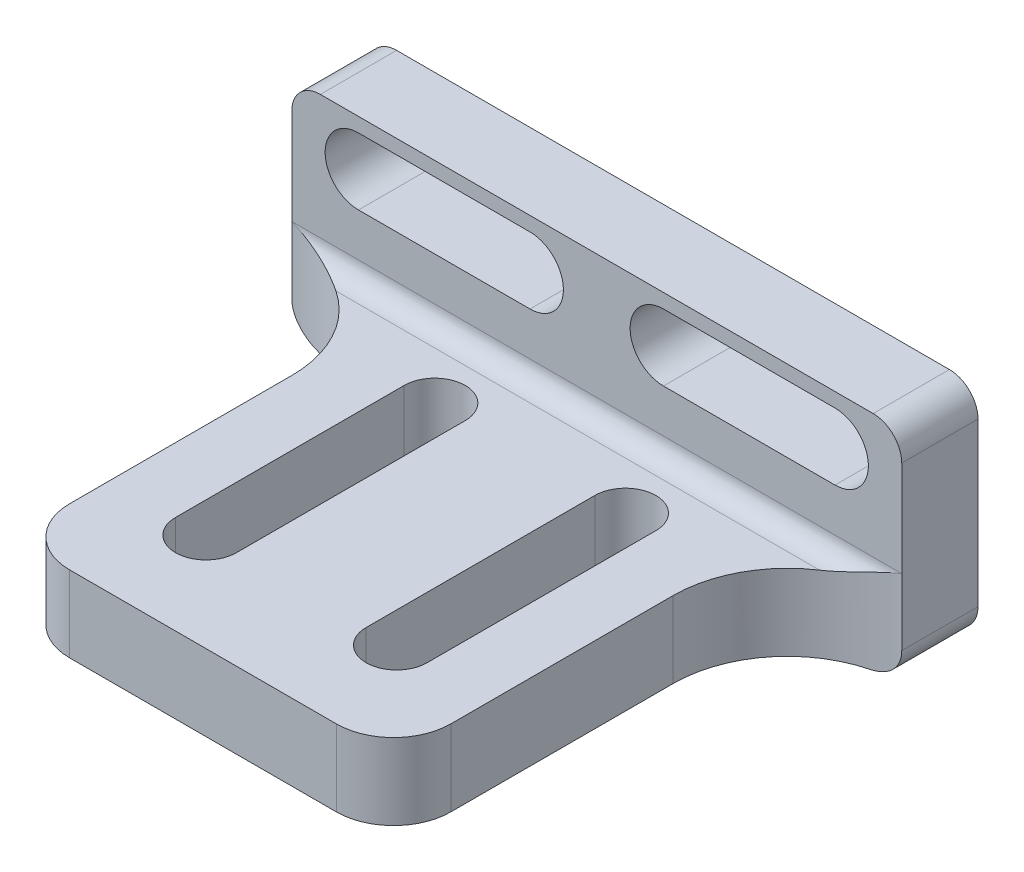
SolidWorks part; units mm, degrees
ref_plane "前视基准面" through (0, 0, 0) normal (0, 0, 1) x (1, 0, 0)
ref_plane "上视基准面" through (0, 0, 0) normal (0, 1, 0) x (1, 0, 0)
ref_plane "右视基准面" through (0, 0, 0) normal (1, 0, 0) x (0, 0, -1)
sketch "草图1" plane through (0, 0, 0) normal (0, 0, 1) x (1, 0, 0)
  line L0 (0, 148.5) -> (0, -94.9538) construction
  line L1 (105, -148.5) -> (-105, -148.5) construction
  line L2 (105, -148.5) -> (105, 148.5) construction
  line L3 (105, 148.5) -> (-105, 148.5) construction
  line L4 (-105, -148.5) -> (-105, 148.5) construction
  line L5 (105, -148.5) -> (-105, 148.5) construction
  line L6 (105, 148.5) -> (-105, -148.5) construction
  line L7 (35.8892, 121.6645) -> (-35.8892, 121.6645)
  line L8 (-35.8892, 121.6645) -> (-66.9017, 102.292)
  line L9 (-75, 40.9339) -> (-75, 31.2613)
  line L10 (-66.9017, 102.292) -> (-66.9017, 52.8701)
  line L11 (75, 40.9339) -> (75, 31.2613)
  line L12 (66.9017, 102.292) -> (66.9017, 52.8701)
  line L13 (35.8892, 121.6645) -> (66.9017, 102.292)
  line L14 (-75, 31.2613) -> (75, 31.2613)
  line L15 (-60, -148.5) -> (-60, -91.8129)
  line L16 (-75, 23.94) -> (75, 23.94)
  line L17 (-75, 23.94) -> (-75, 10.5626)
  line L18 (-38.8455, -105.5906) -> (-66.4608, -113.7617)
  line L19 (-66.4608, -113.7617) -> (-70.1743, -102.7328)
  line L20 (75, 23.94) -> (75, 10.5626)
  line L21 (66.4608, -113.7617) -> (70.1743, -102.7328)
  line L22 (38.8455, -105.5906) -> (66.4608, -113.7617)
  line L23 (-105, 93.0519) -> (105, 93.0519)
  line L24 (-105, 63.0519) -> (105, 63.0519)
  line L25 (-105, -90.0629) -> (-70.5337, -90.0629)
  line L26 (-105, -60.0629) -> (-67.4027, -60.0629)
  line L27 (60, -148.5) -> (60, 148.5)
  line L28 (-60, -58.3129) -> (-45, -58.3129)
  line L29 (-60, -61.8129) -> (-45, -61.8129)
  line L30 (-36, -58.3129) -> (-21, -58.3129)
  line L31 (-36, -61.8129) -> (-21, -61.8129)
  line L32 (-60, -88.3129) -> (-45, -88.3129)
  line L33 (-60, -91.8129) -> (-45, -91.8129)
  line L34 (-36, -88.3129) -> (-21, -88.3129)
  line L35 (-36, -91.8129) -> (-21, -91.8129)
  line L36 (-60, -58.3129) -> (-60, 148.5)
  line L37 (-19.25, -90.0629) -> (105, -90.0629)
  line L38 (-19.25, -60.0629) -> (19.25, -60.0629)
  line L39 (-60, -88.3129) -> (-60, -61.8129)
  line L40 (21, -58.3129) -> (36, -58.3129)
  line L41 (45, -58.3129) -> (60, -58.3129)
  line L42 (60, -61.8129) -> (45, -61.8129)
  line L43 (36, -61.8129) -> (21, -61.8129)
  line L44 (21, -88.3129) -> (36, -88.3129)
  line L45 (21, -91.8129) -> (36, -91.8129)
  line L46 (45, -88.3129) -> (60, -88.3129)
  line L47 (45, -91.8129) -> (60, -91.8129)
  line L48 (37.75, -60.0629) -> (43.25, -60.0629)
  line L49 (58.25, -60.0629) -> (105, -60.0629)
  line L50 (-60, 94.8019) -> (-45, 94.8019)
  line L51 (-36, 94.8019) -> (-21, 94.8019)
  line L52 (-60, 91.3019) -> (-45, 91.3019)
  line L53 (-36, 91.3019) -> (-21, 91.3019)
  line L54 (-60, 64.8019) -> (-45, 64.8019)
  line L55 (-60, 61.3019) -> (-45, 61.3019)
  line L56 (-36, 64.8019) -> (-21, 64.8019)
  line L57 (-36, 61.3019) -> (-21, 61.3019)
  line L58 (21, 94.8019) -> (36, 94.8019)
  line L59 (21, 91.3019) -> (36, 91.3019)
  line L60 (45, 94.8019) -> (60, 94.8019)
  line L61 (45, 91.3019) -> (60, 91.3019)
  line L62 (21, 61.3019) -> (36, 61.3019)
  line L63 (21, 64.8019) -> (36, 64.8019)
  line L64 (45, 61.3019) -> (60, 61.3019)
  line L65 (45, 64.8019) -> (60, 64.8019)
  line L66 (-33.1709, -104.7687) -> (33.1709, -104.7687)
  line L67 (0, -104.7687) -> (0, -148.5) construction
  arc A0 (-75, 40.9339) -> (-66.9017, 52.8701) centre (-79.7474, 52.8701) ccw
  arc A1 (75, 40.9339) -> (66.9017, 52.8701) centre (79.7474, 52.8701) cw
  arc A3 (-60, -88.3129) -> (-60, -91.8129) centre (-60, -90.0629) ccw
  arc A4 (-60, -58.3129) -> (-60, -61.8129) centre (-60, -60.0629) ccw
  circle A5 centre (-60, 63.0519) radius 1.75
  circle A6 centre (-60, 93.0519) radius 1.75
  circle A7 centre (60, 93.0519) radius 1.75
  circle A8 centre (60, 63.0519) radius 1.75
  arc A9 (60, -91.8129) -> (60, -88.3129) centre (60, -90.0629) ccw
  arc A10 (60, -61.8129) -> (60, -58.3129) centre (60, -60.0629) ccw
  arc A11 (-36, -58.3129) -> (-36, -61.8129) centre (-36, -60.0629) ccw
  arc A12 (-36, -88.3129) -> (-36, -91.8129) centre (-36, -90.0629) ccw
  arc A13 (36, -61.8129) -> (36, -58.3129) centre (36, -60.0629) ccw
  arc A14 (36, -91.8129) -> (36, -88.3129) centre (36, -90.0629) ccw
  arc A15 (-45, -61.8129) -> (-45, -58.3129) centre (-45, -60.0629) ccw
  arc A16 (-21, -61.8129) -> (-21, -58.3129) centre (-21, -60.0629) ccw
  arc A17 (-45, -91.8129) -> (-45, -88.3129) centre (-45, -90.0629) ccw
  arc A18 (-21, -91.8129) -> (-21, -88.3129) centre (-21, -90.0629) ccw
  arc A19 (45, -58.3129) -> (45, -61.8129) centre (45, -60.0629) ccw
  arc A20 (21, -58.3129) -> (21, -61.8129) centre (21, -60.0629) ccw
  arc A21 (21, -88.3129) -> (21, -91.8129) centre (21, -90.0629) ccw
  arc A22 (45, -88.3129) -> (45, -91.8129) centre (45, -90.0629) ccw
  circle A23 centre (-36, 93.0519) radius 1.75
  circle A24 centre (-36, 63.0519) radius 1.75
  circle A25 centre (36, 93.0519) radius 1.75
  circle A26 centre (36, 63.0519) radius 1.75
  circle A27 centre (-45, 93.0519) radius 1.75
  circle A28 centre (-21, 93.0519) radius 1.75
  circle A29 centre (-45, 63.0519) radius 1.75
  circle A30 centre (-21, 63.0519) radius 1.75
  circle A31 centre (21, 93.0519) radius 1.75
  circle A32 centre (21, 63.0519) radius 1.75
  circle A33 centre (45, 93.0519) radius 1.75
  circle A34 centre (45, 63.0519) radius 1.75
  arc A35 (33.1709, -104.7687) -> (38.8455, -105.5906) centre (33.1709, -124.7687) cw
  arc A36 (-33.1709, -104.7687) -> (-38.8455, -105.5906) centre (-33.1709, -124.7687) ccw
  spline S0 degree 3 poles (-75, 10.5626) (-72.6959, 1.9073) (-70.3396, -13.3728) (-67.1028, -43.6255) (-66.7657, -72.9327) (-71.8903, -95.1489) (-70.1743, -102.7328) knots 0 0 0 0 0.235247 0.406294 0.801186 1 1 1 1
  spline S1 degree 3 poles (75, 10.5626) (72.6959, 1.9073) (70.3396, -13.3728) (67.1028, -43.6255) (66.7657, -72.9327) (71.8903, -95.1489) (70.1743, -102.7328) knots 0 0 0 0 0.235247 0.406294 0.801186 1 1 1 1
  point P0 (0, 0)
  point P27 (0, 121.6645)
  point P42 (0, -94.0966)
  dimension "D1" = 60
  dimension "D4" = 20
  dimension "D5" = 24
  dimension "D7" = 24
  dimension "D9" = 15
  dimension "D10" = 15
  dimension "D13" = 24
  dimension "D17" = 15
  dimension "D2" = 30
  dimension "D3" = 30
  dimension "D6" = 24
  dimension "D8" = 24
  dimension "D11" = 15
  dimension "D12" = 15
  dimension "D14" = 24
  dimension "D15" = 24
  dimension "D16" = 24
  dimension "D18" = 15
  dimension "D19" = 15
  dimension "D20" = 15
  dimension "D21" = 15
  dimension "D22" = 15
  dimension "D23" = 15
  dimension "D24" = 15
  dimension "D25" = 15
  dimension "D26" = 15
  dimension "D27" = 15
  dimension "D28" = 15
  dimension "D29" = 3.5
  dimension "D30" = 3.5
  dimension "D31" = 3.5
extrude "凸台-拉伸1" add sketch "草图1" along normal blind 3 contours A34 L24 A26 L62 A32 A30 L57 A24 A29 L55 L36 L14 L27 L64 | A5 L24 L10 A0 L9 L14 L36 | A6 L23 L10 L24 A5 L36 | A6 L36 L8 L10 L23 | A33 L60 L27 L13 L7 L8 L36 L50 A27 L23 A23 L51 A28 A31 L58 A25 | A34 L65 L27 L61 A33 L23 A25 L59 A31 A28 L53 A23 A27 L52 L36 L54 A29 L24 A24 L56 A30 A32 L63 A26 | A7 L23 L12 L13 L27 | A8 L24 L12 L23 A7 L27 | A8 L27 L14 L11 A1 L12 L24 | A22 L46 L27 L42 A19 A13 L43 A20 A16 L31 A11 L30 L40 L41 L16 L36 L28 A15 L29 L39 L32 A17 L33 L15 L18 L22 L47 A14 L45 A21 A18 L35 A12 L34 | L17 S0 L19 L18 L15 A3 L39 A4 L36 L16 | S1 L20 L16 L27 A10 L49 | S1 L49 A10 L27 A9 L37 | S1 L37 A9 L27 L22 L21 region at (0, 106.7597, 0) region at (63.3118, 98.9762, 0) region at (-63.3118, 98.9762, 0) region at (63.5153, 78.0519, 0) region at (-63.5153, 78.0519, 0) region at (65.7633, 44.067, 0) region at (0, 78.0519, 0) region at (-65.7633, 44.067, 0) region at (0, 46.6707, 0) region at (0, -40.0712, 0) region at (65.6849, -11.6712, 0) region at (-65.3451, -38.0027, 0) region at (64.4303, -76.0355, 0) region at (65.0264, -100.7629, 0)
sketch "草图7" plane through (0, 0, 0) normal (0, 0, -1) x (-1, 0, 0)
  line L0 (0, 121.6645) -> (0, -104.7687) construction
  line L1 (-35.8892, 121.6645) -> (35.8892, 121.6645) construction
  line L2 (33.1709, -104.7687) -> (-33.1709, -104.7687) construction
  line L3 (0, 41.2613) -> (-21, 41.2613) construction
  line L4 (0, 41.2613) -> (21, 41.2613) construction
  line L5 (0, 13.94) -> (-21, 13.94) construction
  line L6 (0, 13.94) -> (21, 13.94) construction
  line L7 (75, 23.94) -> (-75, 23.94) construction
  line L8 (75, 31.2613) -> (-75, 31.2613) construction
  circle A0 centre (-21, 41.2613) radius 2.25
  circle A1 centre (21, 41.2613) radius 2.25
  circle A2 centre (-21, 13.94) radius 2.25
  circle A3 centre (21, 13.94) radius 2.25
  dimension "D1" = 10
  dimension "D2" = 10
extrude "切除-拉伸2" cut sketch "草图7" against normal through all
sketch "草图8" plane through (0, 0, 3) normal (0, 0, 1) x (1, 0, 0)
  line L0 (0, 121.6645) -> (0, -1.9696) construction
  line L1 (35.8892, 121.6645) -> (-35.8892, 121.6645) construction
  line L2 (-33.1709, -104.7687) -> (33.1709, -104.7687) construction
  line L3 (-33.409, 20.409) -> (-12.6214, -0.3786)
  line L4 (31.818, -51.182) -> (-31.818, -51.182)
  line L5 (35, -48) -> (35, 15.6418)
  line L8 (-35, 18.818) -> (-12.6214, -3.5605) construction
  line L9 (-33.409, -52.773) -> (-12.5737, -31.9377)
  line L10 (-36.591, 17.227) -> (-15.8034, -3.5605)
  line L11 (33.4105, 20.4105) -> (12.573, -0.427)
  line L12 (15.803, -3.5609) -> (36.5881, 17.2241)
  line L13 (31.8195, 18.8195) -> (-31.818, 18.818)
  line L14 (-15.8038, -28.8038) -> (-36.591, -49.591)
  line L15 (12.5534, -31.9174) -> (33.409, -52.773)
  line L16 (34.9993, 18.8173) -> (12.6207, -3.5613) construction
  line L17 (0, -30.3951) -> (0, -104.7687) construction
  line L18 (-35, -48) -> (-35, 15.636)
  line L19 (-11.9624, -1.9696) -> (-14.2124, -1.9696) construction
  line L20 (15.8034, -28.8034) -> (36.591, -49.591)
  line L21 (14.2117, -30.3951) -> (11.9607, -30.3951) construction
  line L22 (14.2117, -30.3951) -> (14.2117, -28.1441) construction
  line L23 (14.2117, -1.9696) -> (11.9612, -1.9696) construction
  line L24 (-14.2124, -30.3951) -> (-14.2124, -28.1446) construction
  line L25 (14.2117, -30.3951) -> (12.62, -28.8034) construction
  line L26 (14.2117, -1.9696) -> (12.6204, -3.5609) construction
  line L27 (12.6207, -28.8027) -> (35, -51.182) construction
  line L28 (-12.6215, -3.5606) -> (-14.2124, -1.9696) construction
  line L29 (-14.2124, -4.2196) -> (-14.2124, -1.9696) construction
  line L30 (-12.6214, -28.8034) -> (-35, -51.182) construction
  line L31 (-12.6211, -28.8037) -> (-14.2124, -30.3951) construction
  line L32 (-11.9619, -30.3951) -> (-14.2124, -30.3951) construction
  line L33 (14.2117, -4.2201) -> (14.2117, -1.9696) construction
  line L34 (11.0312, -30.3951) -> (0, -30.3951) construction
  arc A0 (-33.409, 20.409) -> (-36.591, 17.227) centre (-35, 18.818) ccw
  arc A1 (36.5881, 17.2241) -> (33.4105, 20.4105) centre (34.9993, 18.8173) ccw
  arc A2 (-36.591, -49.591) -> (-33.409, -52.773) centre (-35, -51.182) ccw
  arc A3 (33.409, -52.773) -> (36.591, -49.591) centre (35, -51.182) ccw
  arc A4 (-15.8034, -3.5605) -> (-12.6214, -0.3786) centre (-14.2124, -1.9696) ccw
  arc A5 (12.6692, -0.3308) -> (15.803, -3.5609) centre (14.2117, -1.9696) ccw
  arc A6 (-12.6699, -32.0338) -> (-15.8038, -28.8038) centre (-14.2124, -30.3951) ccw
  arc A7 (15.8034, -28.8034) -> (12.6894, -32.0534) centre (14.2117, -30.3951) ccw
  circle A8 centre (-0.0004, -16.1823) radius 8
  point P6 (0, -16.182)
  point P13 (-0.0004, -16.1823)
extrude "切除-拉伸3" cut sketch "草图8" against normal through all contours L10 A4 L3 A0 | L11 A5 L12 A1 | L20 A7 L15 A3 | L9 A6 L14 A2 | A8 region at (-24.6062, 8.4242, 3) region at (24.6054, 8.4234, 3) region at (-24.6061, -40.7881, 3) region at (24.6056, -40.7877, 3) region at (-0.0004, -16.1823, 3)
sketch "草图9" plane through (0, 0, 3) normal (0, 0, 1) x (1, 0, 0)
  line L0 (-70.7828, -98.747) -> (70.7828, -98.747) construction
  line L1 (0, -98.747) -> (0, -104.7687) construction
  line L2 (55, -100.497) -> (20, -100.497)
  line L3 (-55, -96.997) -> (-20, -96.997)
  line L4 (-55, -100.497) -> (-20, -100.497)
  line L5 (-33.1709, -104.7687) -> (33.1709, -104.7687) construction
  line L6 (55, -96.997) -> (20, -96.997)
  arc A0 (-55, -96.997) -> (-55, -100.497) centre (-55, -98.747) ccw
  arc A1 (-20, -100.497) -> (-20, -96.997) centre (-20, -98.747) ccw
  arc A2 (20, -100.497) -> (20, -96.997) centre (20, -98.747) cw
  arc A3 (55, -96.997) -> (55, -100.497) centre (55, -98.747) cw
  spline S0 degree 3 poles (-75, 10.5626) (-72.6959, 1.9073) (-70.3396, -13.3728) (-67.1028, -43.6255) (-66.7657, -72.9327) (-71.8903, -95.1489) (-70.1743, -102.7328) knots 0 0 0 0 0.235247 0.406294 0.801186 1 1 1 1 construction
  spline S1 degree 3 poles (75, 10.5626) (72.6959, 1.9073) (70.3396, -13.3728) (67.1028, -43.6255) (66.7657, -72.9327) (71.8903, -95.1489) (70.1743, -102.7328) knots 0 0 0 0 0.235247 0.406294 0.801186 1 1 1 1 construction
  dimension "D1" = 35
  dimension "D2" = 20
extrude "切除-拉伸4" cut sketch "草图9" against normal blind 3
sketch "草图10" plane through (0, 0, 3) normal (0, 0, 1) x (1, 0, 0)
  line L0 (-21, -60.0629) -> (-21, -90.0629) construction
  line L1 (21, -60.0629) -> (21, -90.0629) construction
  line L2 (-21, -75.0629) -> (-17.5, -75.0629) construction
  line L4 (12.5, -80.0629) -> (-12.5, -80.0629)
  line L6 (12.5, -70.0629) -> (-12.5, -70.0629)
  line L11 (17.5, -75.0629) -> (21, -75.0629) construction
  arc A0 (-12.5, -70.0629) -> (-12.5, -80.0629) centre (-12.5, -75.0629) ccw
  arc A1 (12.5, -80.0629) -> (12.5, -70.0629) centre (12.5, -75.0629) ccw
  point P11 (0, -75.0629)
extrude "切除-拉伸5" cut sketch "草图10" against normal blind 3
sketch "草图11" plane through (0, 0, 3) normal (0, 0, 1) x (1, 0, 0)
  line L0 (-21, 93.0519) -> (-21, 63.0519) construction
  line L1 (21, 93.0519) -> (21, 63.0519) construction
  line L2 (-21, 78.0519) -> (-20, 78.0519) construction
  line L4 (15, 73.0519) -> (-15, 73.0519)
  line L6 (15, 83.0519) -> (-15, 83.0519)
  line L10 (20, 78.0519) -> (21, 78.0519) construction
  arc A0 (-15, 83.0519) -> (-15, 73.0519) centre (-15, 78.0519) ccw
  arc A1 (15, 73.0519) -> (15, 83.0519) centre (15, 78.0519) ccw
  point P10 (0, 78.0519)
  dimension "D1" = 30
extrude "切除-拉伸8" cut sketch "草图11" against normal blind 3
sketch "草图12" plane through (0, 0, 3) normal (0, 0, 1) x (1, 0, 0)
  line L0 (0, 121.6645) -> (0, 83.0519) construction
  line L1 (35.8892, 121.6645) -> (-35.8892, 121.6645) construction
  line L2 (15, 83.0519) -> (-15, 83.0519) construction
  circle A0 centre (0, 106.3718) radius 11 construction
  circle A1 centre (0, 106.3718) radius 8 construction
  circle A2 centre (0, 114.3718) radius 1.7
  circle A3 centre (0, 98.3718) radius 1.7
  circle A4 centre (8, 106.3718) radius 1.7
  circle A5 centre (-8, 106.3718) radius 1.7
extrude "切除-拉伸9" cut sketch "草图12" against normal blind 3
sketch "草图13" plane through (0, 0, 3) normal (0, 0, 1) x (1, 0, 0)
  line L0 (0, -104.7687) -> (0, -80.0629) construction
  line L1 (-33.1709, -104.7687) -> (33.1709, -104.7687) construction
  line L2 (-12.5, -80.0629) -> (12.5, -80.0629) construction
  circle A0 centre (0, -92.4158) radius 8 construction
  circle A1 centre (0, -84.4158) radius 1.7
  circle A2 centre (8, -92.4158) radius 1.7
  circle A3 centre (0, -100.4158) radius 1.7
  circle A4 centre (-8, -92.4158) radius 1.7
extrude "切除-拉伸11" cut sketch "草图13" against normal blind 3
sketch "草图14" plane through (0, 0, 3) normal (0, 0, 1) x (1, 0, 0)
  line L0 (0, 23.94) -> (0, -104.7687) construction
  line L1 (-55.4755, 8.9197) -> (-55.4755, -46.0803)
  line L2 (-58.9755, 8.9197) -> (-58.9755, -46.0803)
  line L3 (-75, 23.94) -> (75, 23.94) construction
  line L4 (-33.1709, -104.7687) -> (33.1709, -104.7687) construction
  line L5 (58.9755, 8.9197) -> (58.9755, -46.0803)
  line L6 (55.4755, 8.9197) -> (55.4755, -46.0803)
  arc A0 (-55.4755, 8.9197) -> (-58.9755, 8.9197) centre (-57.2255, 8.9197) ccw
  arc A1 (-58.9755, -46.0803) -> (-55.4755, -46.0803) centre (-57.2255, -46.0803) ccw
  arc A2 (58.9755, -46.0803) -> (55.4755, -46.0803) centre (57.2255, -46.0803) cw
  arc A3 (55.4755, 8.9197) -> (58.9755, 8.9197) centre (57.2255, 8.9197) cw
extrude "切除-拉伸12" cut sketch "草图14" against normal through all
fillet "圆角1" radius 2 2 edges at (75, 31.2613, 1.5) (-75, 31.2613, 1.5)
fillet "圆角2" radius 2 2 edges at (-75, 23.94, 1.5) (75, 23.94, 1.5)
sketch "草图15" plane through (0, 0, 0) normal (0, 0, -1) x (-1, 0, 0)
  line L0 (0, 121.6645) -> (0, 31.2613) construction
  line L1 (-35.8892, 121.6645) -> (35.8892, 121.6645) construction
  line L2 (73, 31.2613) -> (-73, 31.2613) construction
  line L3 (-27.5188, 121.6645) -> (-63.6963, 99.0657) construction
  line L4 (-35.8892, 121.6645) -> (-66.9017, 102.292) construction
  line L5 (-61.1842, 102.4035) -> (-34.7748, 118.9006)
  line L6 (-59.5948, 99.8591) -> (-33.1854, 116.3562)
  line L7 (27.5188, 121.6645) -> (63.6963, 99.0657) construction
  line L8 (59.5948, 99.8591) -> (33.1854, 116.3562)
  line L9 (61.1842, 102.4035) -> (34.7748, 118.9006)
  arc A0 (-61.1842, 102.4035) -> (-59.5948, 99.8591) centre (-60.3895, 101.1313) ccw
  arc A1 (-33.1854, 116.3562) -> (-34.7748, 118.9006) centre (-33.9801, 117.6284) ccw
  arc A2 (33.1854, 116.3562) -> (34.7748, 118.9006) centre (33.9801, 117.6284) cw
  arc A3 (61.1842, 102.4035) -> (59.5948, 99.8591) centre (60.3895, 101.1313) cw
extrude "切除-拉伸13" cut sketch "草图15" against normal through all
sketch "草图16" plane through (0, 0, 0) normal (0, 0, -1) x (-1, 0, 0)
  line L0 (0, 121.6645) -> (0, 31.2613) construction
  line L1 (-35.8892, 121.6645) -> (35.8892, 121.6645) construction
  line L2 (73, 31.2613) -> (-73, 31.2613) construction
  line L3 (-21, 41.2613) -> (-66.71, 41.2613) construction
  line L4 (-61.517, 42.7613) -> (-32.0563, 42.7613)
  line L5 (-61.517, 39.7613) -> (-32.0563, 39.7613)
  line L6 (21, 41.2613) -> (66.71, 41.2613) construction
  line L7 (61.517, 39.7613) -> (32.0563, 39.7613)
  line L8 (61.517, 42.7613) -> (32.0563, 42.7613)
  arc A0 (-61.517, 42.7613) -> (-61.517, 39.7613) centre (-61.517, 41.2613) ccw
  arc A1 (-32.0563, 39.7613) -> (-32.0563, 42.7613) centre (-32.0563, 41.2613) ccw
  arc A2 (32.0563, 39.7613) -> (32.0563, 42.7613) centre (32.0563, 41.2613) cw
  arc A3 (61.517, 42.7613) -> (61.517, 39.7613) centre (61.517, 41.2613) cw
extrude "切除-拉伸14" cut sketch "草图16" against normal through all
sketch "草图17" plane through (0, 0, 0) normal (0, 0, -1) x (-1, 0, 0)
  text T0 "Y" font "黑体" height in points 72
extrude "切除-拉伸15" cut sketch "草图17" against normal through all
sketch "草图18" plane through (0, 0, 0) normal (0, 0, -1) x (-1, 0, 0)
  text T0 "H" font "黑体" height in points 72
extrude "切除-拉伸16" cut sketch "草图18" against normal through all
ref_plane "基准面1" through (0, 0, 13) normal (0, 0, 1) x (1, 0, 0)
sketch "草图19" plane through (0, 0, 13) normal (0, 0, 1) x (1, 0, 0)
  line L2 (20, -100.497) -> (55, -100.497) construction
  line L3 (55, -96.997) -> (20, -96.997) construction
  line L6 (20, -100.497) -> (45, -100.497)
  line L7 (45, -96.997) -> (20, -96.997)
  line L8 (0, -100.4158) -> (0, -70.0629) construction
  line L9 (12.5, -70.0629) -> (-12.5, -70.0629) construction
  line L10 (45, -98.747) -> (20, -98.747) construction
  line L11 (-16.5, -96.247) -> (-43.7, -100.497) construction
  line L12 (16.5, -101.247) -> (16.5, -104.7687) construction
  line L14 (16.5, -101.247) -> (16.5, -96.247)
  line L15 (16.5, -96.247) -> (48.5, -96.247)
  line L16 (48.5, -101.247) -> (48.5, -96.247)
  line L17 (16.5, -101.247) -> (48.5, -96.247) construction
  line L18 (16.5, -96.247) -> (43.7, -100.497) construction
  line L19 (-33.1709, -104.7687) -> (33.1709, -104.7687) construction
  line L21 (48.5, -101.247) -> (48.5, -104.7687)
  line L22 (48.5, -104.7687) -> (16.5, -104.7687)
  line L23 (16.5, -101.247) -> (16.5, -104.7687)
  line L24 (-16.5, -101.247) -> (-48.5, -96.247) construction
  line L25 (-16.5, -101.247) -> (-16.5, -104.7687) construction
  line L26 (-45, -98.747) -> (-20, -98.747) construction
  line L27 (-16.5, -101.247) -> (-16.5, -104.7687)
  line L28 (-48.5, -104.7687) -> (-16.5, -104.7687)
  line L29 (-48.5, -101.247) -> (-48.5, -104.7687)
  line L30 (-48.5, -101.247) -> (-48.5, -96.247)
  line L31 (-16.5, -96.247) -> (-48.5, -96.247)
  line L32 (-16.5, -101.247) -> (-16.5, -96.247)
  line L33 (-45, -96.997) -> (-20, -96.997)
  line L34 (-20, -100.497) -> (-45, -100.497)
  arc A0 (-45, -100.497) -> (-45, -96.997) centre (-45, -98.747) cw
  arc A2 (20, -96.997) -> (20, -100.497) centre (20, -98.747) ccw construction
  arc A3 (-20, -96.997) -> (-20, -100.497) centre (-20, -98.747) cw
  arc A6 (20, -96.997) -> (20, -100.497) centre (20, -98.747) ccw
  arc A8 (45, -100.497) -> (45, -96.997) centre (45, -98.747) ccw
  point P2 (32.5, -98.747)
  point P36 (-32.5, -98.747)
extrude "凸台-拉伸2" add sketch "草图19" along normal blind 4 separate body
sketch "草图21" plane through (0, 0, 17) normal (0, 0, 1) x (1, 0, 0)
  line L0 (-46.75, -98.747) -> (-18.25, -98.747) construction
  line L1 (-32.5, -96.997) -> (-32.5, -100.497) construction
  line L2 (-20, -96.997) -> (-45, -96.997) construction
  line L3 (-45, -100.497) -> (-20, -100.497) construction
  line L4 (-36, -96.997) -> (-29, -96.997)
  line L5 (-36, -100.497) -> (-29, -100.497)
  line L6 (0, -104.7687) -> (0, -70.0629) construction
  line L7 (-33.1709, -104.7687) -> (33.1709, -104.7687) construction
  line L8 (12.5, -70.0629) -> (-12.5, -70.0629) construction
  line L9 (32.5, -96.997) -> (32.5, -100.497) construction
  line L10 (36, -100.497) -> (29, -100.497)
  line L11 (36, -96.997) -> (29, -96.997)
  arc A0 (-45, -96.997) -> (-45, -100.497) centre (-45, -98.747) ccw construction
  arc A1 (-20, -100.497) -> (-20, -96.997) centre (-20, -98.747) ccw construction
  arc A2 (-36, -100.497) -> (-36, -96.997) centre (-36, -98.747) ccw
  arc A3 (-29, -96.997) -> (-29, -100.497) centre (-29, -98.747) ccw
  arc A4 (29, -96.997) -> (29, -100.497) centre (29, -98.747) cw
  arc A5 (36, -100.497) -> (36, -96.997) centre (36, -98.747) cw
  point P18 (-32.5, -98.747)
  dimension "D1" = 3.5
  dimension "D2" = 3.5
extrude "凸台-拉伸4" add sketch "草图21" against normal up to surface (4 mm away) up to face at (32.5, -100.5079, 13)
sketch "草图23" plane through (0, 0, 13) normal (0, 0, 1) x (1, 0, 0)
  line L0 (-16.5, -104.7687) -> (-16.5, -120.6552) construction
  line L1 (48.5, -104.7687) -> (48.5, -120.6552) construction
  line L2 (-16.5, -104.7687) -> (-16.5, -96.247) construction
  line L4 (-48.5, -104.7687) -> (-48.5, -107.7687)
  line L5 (-48.5, -107.7687) -> (-16.5, -107.7687)
  line L6 (-16.5, -104.7687) -> (-16.5, -107.7687)
  line L8 (16.5, -104.7687) -> (16.5, -107.7687)
  line L9 (16.5, -107.7687) -> (48.5, -107.7687)
  line L10 (48.5, -104.7687) -> (48.5, -107.7687)
  line L12 (-48.5, -104.7687) -> (-48.5, -102.7687)
  line L13 (-48.5, -102.7687) -> (-16.5, -102.7687)
  line L14 (-16.5, -104.7687) -> (-16.5, -102.7687)
  line L17 (16.5, -104.7687) -> (16.5, -102.7687)
  line L18 (16.5, -102.7687) -> (48.5, -102.7687)
  line L19 (48.5, -104.7687) -> (48.5, -102.7687)
extrude "凸台-拉伸5" add sketch "草图23" along normal blind 35
sketch "草图25" plane through (0, -102.7687, 0) normal (0, 1, 0) x (1, 0, 0)
  line L0 (-32.5, -17) -> (-32.5, -48) construction
  line L1 (-16.5, -17) -> (-48.5, -17) construction
  line L2 (-16.5, -48) -> (-48.5, -48) construction
  line L3 (-22.5, -17) -> (-22.5, -48)
  line L4 (-48.5, -17) -> (-42.5, -17)
  line L5 (-48.5, -17) -> (-48.5, -48)
  line L6 (-48.5, -48) -> (-42.5, -48)
  line L7 (-42.5, -17) -> (-42.5, -48)
  line L8 (-16.5, -17) -> (-16.5, -48)
  line L9 (-16.5, -17) -> (-22.5, -17)
  line L10 (-16.5, -48) -> (-22.5, -48)
  line L11 (0, 0) -> (0, -48) construction
  line L12 (32.5, -17) -> (32.5, -48) construction
  line L13 (16.5, -48) -> (22.5, -48)
  line L14 (16.5, -17) -> (22.5, -17)
  line L15 (16.5, -17) -> (16.5, -48)
  line L16 (42.5, -17) -> (42.5, -48)
  line L17 (48.5, -48) -> (42.5, -48)
  line L18 (48.5, -17) -> (48.5, -48)
  line L19 (48.5, -17) -> (42.5, -17)
  line L20 (22.5, -17) -> (22.5, -48)
extrude "切除-拉伸17" cut sketch "草图25" against normal up to surface (5 mm away) up to face at (-32.5, -107.7687, 30.5)
fillet "圆角3" radius 6 2 edges at (22.5, -105.2687, 17) (42.5, -105.2687, 17)
fillet "圆角4" radius 6 2 edges at (-42.5, -105.2687, 17) (-22.5, -105.2687, 17)
fillet "圆角5" radius 1.5 4 edges at (48.5, -107.7687, 15) (16.5, -107.7687, 15) (16.5, -96.247, 15) (48.5, -96.247, 15)
fillet "圆角6" radius 1.5 4 edges at (-48.5, -107.7687, 15) (-48.5, -96.247, 15) (-16.5, -96.247, 15) (-16.5, -107.7687, 15)
sketch "草图26" plane through (0, -107.7687, 0) normal (0, -1, 0) x (1, 0, 0)
  line L0 (0, 0) -> (0, 51.2514) construction
  line L2 (22.5, 48) -> (42.5, 48) construction
  line L4 (42.5, 48) -> (32.5, 48) construction
  line L6 (75.7359, 13) -> (-75.7359, 13) construction
  line L7 (37.5, 20.5) -> (37.5, 13) construction
  line L9 (35.9, 20.5) -> (35.9, 32.5)
  line L11 (39.1, 20.5) -> (39.1, 32.5)
  line L12 (27.5, 30.9) -> (27.5, 22.1) construction
  line L13 (25.9, 20.5) -> (25.9, 32.5)
  line L14 (37.5, 30.9) -> (37.5, 22.1) construction
  line L15 (29.1, 20.5) -> (29.1, 32.5)
  line L16 (-37.5, 34.1) -> (-37.5, 22.1) construction
  line L17 (-27.5, 34.1) -> (-27.5, 22.1) construction
  line L18 (-29.1, 20.5) -> (-29.1, 32.5)
  line L19 (-25.9, 20.5) -> (-25.9, 32.5)
  line L20 (-39.1, 20.5) -> (-39.1, 32.5)
  line L21 (-35.9, 20.5) -> (-35.9, 32.5)
  arc A1 (35.9, 20.5) -> (39.1, 20.5) centre (37.5, 20.5) ccw
  arc A2 (29.1, 20.5) -> (25.9, 20.5) centre (27.5, 20.5) cw
  arc A5 (-29.1, 20.5) -> (-25.9, 20.5) centre (-27.5, 20.5) ccw
  arc A6 (-35.9, 20.5) -> (-39.1, 20.5) centre (-37.5, 20.5) cw
  arc A8 (39.1, 32.5) -> (35.9, 32.5) centre (37.5, 32.5) ccw
  arc A9 (29.1, 32.5) -> (25.9, 32.5) centre (27.5, 32.5) ccw
  arc A10 (-29.1, 32.5) -> (-25.9, 32.5) centre (-27.5, 32.5) cw
  arc A11 (-39.1, 32.5) -> (-35.9, 32.5) centre (-37.5, 32.5) cw
  point P15 (37.5, 30.5)
  point P32 (27.5, 30.5)
  point P49 (-27.5, 30.5)
  point P50 (-37.5, 30.5)
  dimension "D1" = 12
extrude "切除-拉伸18" cut sketch "草图26" against normal blind 5
sketch "草图27" plane through (42.5, 0, 0) normal (1, 0, 0) x (0, 0, -1)
  line L0 (-17, -106.2687) -> (-17, -102.7687) construction
  line L1 (-48, -102.7687) -> (-17, -102.7687)
  line L2 (-48, -102.7687) -> (-48, -103.7687)
  line L3 (-48, -103.7687) -> (-17, -103.7687)
  line L4 (-17, -102.7687) -> (-17, -103.7687)
extrude "切除-拉伸19" cut sketch "草图27" against normal blind 95 and the other way blind 15
fillet "圆角8" radius 1 1 edges at (-32.5, -103.7687, 17)
fillet "圆角9" radius 1 1 edges at (32.5, -103.7687, 17)
fillet "圆角10" radius 3 2 edges at (-22.5, -105.7687, 48) (-42.5, -105.7687, 48)
sketch "草图28" plane through (0, -107.7687, 0) normal (0, -1, 0) x (1, 0, 0)
  line L0 (-42.5, 23) -> (-42.5, 45) construction
  line L1 (42.5, 48) -> (-42.5, 48)
  line L2 (42.5, 48) -> (42.5, 37.6569)
  line L3 (42.5, 37.6569) -> (-42.5, 37.6569)
  line L4 (-42.5, 48) -> (-42.5, 37.6569)
extrude "切除-拉伸20" cut sketch "草图28" against normal blind 5
fillet "圆角12" radius 3 2 edges at (22.5, -105.7687, 37.6569) (42.5, -105.7687, 37.6569)
fillet "圆角13" radius 3 2 edges at (-42.5, -105.7687, 37.6569) (-22.5, -105.7687, 37.6569)
ref_plane "基准面2" through (0, -112.7687, 0) normal (0, -1, 0) x (-1, 0, 0)
sketch "草图31" plane through (0, 121.6645, 0) normal (0, 1, 0) x (1, 0, 0)
  line L1 (-79.0565, 2.2725) -> (80.5534, 2.2725)
  line L2 (-79.0565, 2.2725) -> (-79.0565, -7.1241)
  line L3 (-79.0565, -7.1241) -> (80.5534, -7.1241)
  line L4 (80.5534, 2.2725) -> (80.5534, -7.1241)
extrude "切除-拉伸21" cut sketch "草图31" against normal blind 265
sketch "草图32" plane through (0, -107.7687, 0) normal (0, -1, 0) x (1, 0, 0)
  line L1 (55.699, 7.5193) -> (10.3758, 7.5193)
  line L2 (55.699, 7.5193) -> (55.699, 47.0609)
  line L3 (55.699, 47.0609) -> (10.3758, 47.0609)
  line L4 (10.3758, 7.5193) -> (10.3758, 47.0609)
extrude "切除-拉伸22" cut sketch "草图32" against normal blind 40
